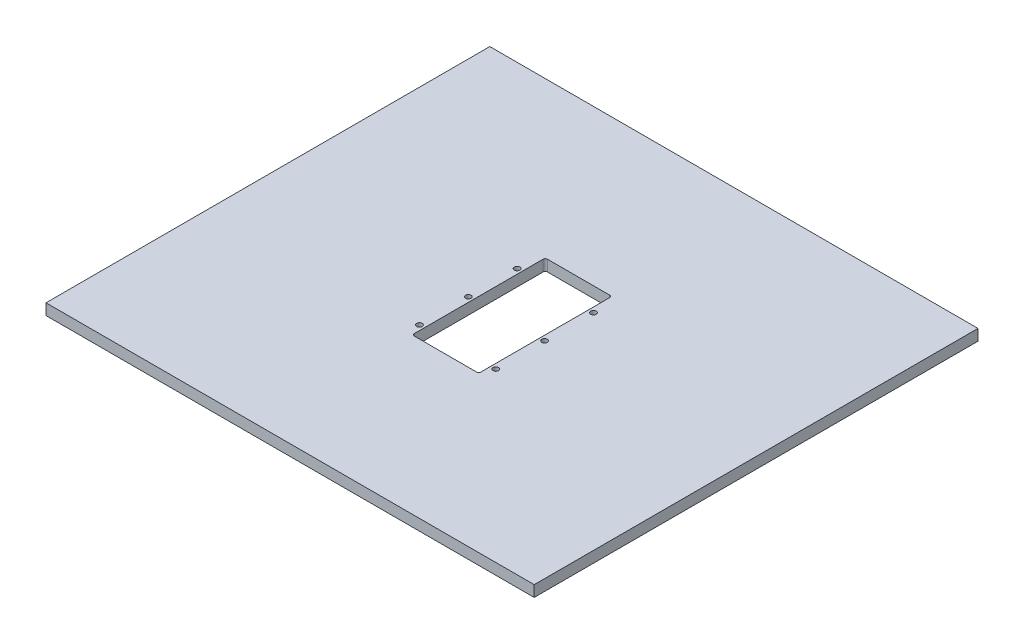
SolidWorks part; units mm, degrees
ref_plane "Plano frontal" through (0, 0, 0) normal (0, 0, 1) x (1, 0, 0)
ref_plane "Plano superior" through (0, 0, 0) normal (0, 1, 0) x (1, 0, 0)
ref_plane "Plano direito" through (0, 0, 0) normal (1, 0, 0) x (0, 0, -1)
sketch "Esboço1" plane through (0, 0, 0) normal (0, 1, 0) x (1, 0, 0)
  line L1 (100, -100) -> (-100, -100)
  line L2 (110, -90) -> (110, 90)
  line L3 (100, 100) -> (-100, 100)
  line L4 (-110, -90) -> (-110, 90)
  line L5 (110, -100) -> (-110, 100) construction
  line L6 (110, 100) -> (-110, -100) construction
  line L7 (110, -100) -> (-110, -100)
  line L8 (110, -100) -> (110, 100)
  line L9 (110, 100) -> (-110, 100)
  line L10 (-110, 0) -> (110, 0) construction
  line L11 (0, 30) -> (0, -30) construction
  line L12 (14, 30) -> (-14, 30)
  line L13 (15, 29) -> (15, -29)
  line L14 (14, -30) -> (-14, -30)
  line L15 (-15, 29) -> (-15, -29)
  line L16 (15, 30) -> (-15, -30) construction
  line L17 (15, -30) -> (-15, 30) construction
  line L18 (-110, -100) -> (-110, 100)
  line L19 (110, -100) -> (-110, 100) construction
  line L20 (110, 100) -> (-110, -100) construction
  circle A8 centre (17.2, 19.5) radius 1.25
  circle A9 centre (17.2, -2.5) radius 1.25
  circle A10 centre (17.2, -24.5) radius 1.25
  arc A11 (15, -29) -> (14, -30) centre (14, -29) cw
  arc A12 (-14, -30) -> (-15, -29) centre (-14, -29) cw
  arc A13 (14, 30) -> (15, 29) centre (14, 29) cw
  arc A14 (-14, 30) -> (-15, 29) centre (-14, 29) ccw
  circle A15 centre (-17.2, -24.5) radius 1.25
  circle A16 centre (-17.2, -2.5) radius 1.25
  circle A17 centre (-17.2, 19.5) radius 1.25
  point P0 (0, 0)
  point P18 (0, 0)
  point P32 (0, 0)
  dimension "D8" = 60
  dimension "D10" = 2.5
  dimension "D13" = 2.5
  dimension "D16" = 2.5
  dimension "D17" = 1
  dimension "D1" = 200
  dimension "D2" = 220
  dimension "D9" = 30
  dimension "D11" = 10.5
  dimension "D12" = 22
  dimension "D14" = 2.2
  dimension "D15" = 22
extrude "Ressalto-extrusão1" add sketch "Esboço1" along normal blind 5 contours L18 L7 L1 L8 L2 L9 L3 L4 A16 A8 A9 A10 A14 L12 A13 L13 A11 L14 A12 L15 A15 A17 region at (0, 0, 97.0268)
